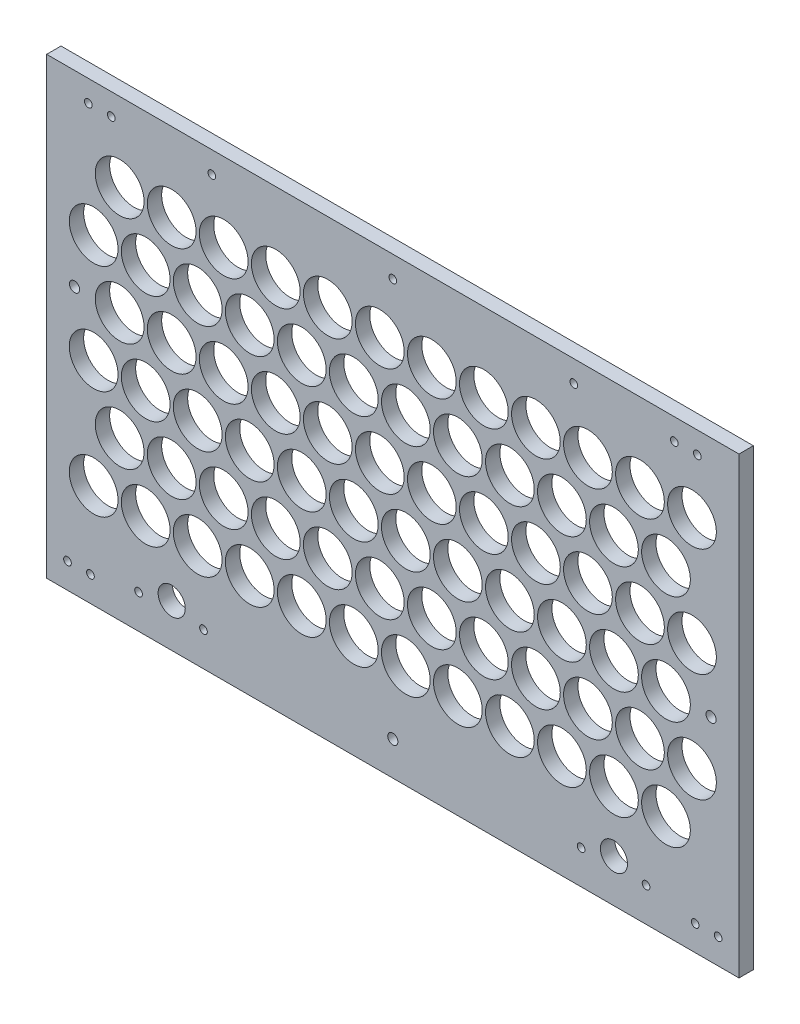
SolidWorks part; units mm, degrees
material "ABS"
ref_plane "X-Y Datum" through (0, 0, 0) normal (0, 0, 1) x (1, 0, 0)
ref_plane "X-Z Datum" through (0, 0, 0) normal (0, 1, 0) x (1, 0, 0)
ref_plane "Y-Z Datum" through (0, 0, 0) normal (1, 0, 0) x (0, 0, -1)
sketch "Sketch1" plane through (0, 0, 0) normal (0, 0, 1) x (1, 0, 0)
  line L1 (-143.025, 70.775) -> (143.025, 70.775)
  line L2 (-143.025, 70.775) -> (-143.025, -70.775)
  line L3 (-143.025, -70.775) -> (143.025, -70.775)
  line L4 (143.025, 70.775) -> (143.025, -70.775)
  line L5 (-143.025, 70.775) -> (143.025, -70.775) construction
  line L6 (-143.025, -70.775) -> (143.025, 70.775) construction
  line L13 (-153.025, -105.775) -> (153.025, -105.775)
  line L14 (-153.025, 91.65) -> (153.025, 91.65)
  line L15 (-153.025, 91.65) -> (-153.025, -105.775)
  line L16 (153.025, 91.65) -> (153.025, -105.775)
  line L17 (153.025, 70.775) -> (153.025, -70.775) construction
  line L18 (-143.025, 91.65) -> (143.025, 91.65) construction
  line L19 (-143.025, -105.775) -> (143.025, -105.775) construction
  line L20 (-153.025, 70.775) -> (-153.025, -70.775) construction
  line L21 (-132.25, -60) -> (-109.25, -60) construction
  circle A0 centre (-132.25, -60) radius 10.775
  circle A1 centre (-109.25, -60) radius 10.775 construction
  circle A2 centre (-120.75, -36) radius 10.775
  point P0 (0, 0)
  point P16 (-120.75, -60)
  dimension "D1" = 21.55
  dimension "D2" = 23
  dimension "D3" = 24
  dimension "D5" = 141.55
  dimension "D6" = 286.05
  dimension "D7" = 35
  dimension "D8" = 20.875
  dimension "D9" = 10
  dimension "D10" = 10
extrude "Boss-Extrude1" add sketch "Sketch1" along normal blind 6.35 contours A0 L3 L4 L1 L2 A2 | A2 | A0 | A0 L2 L3 | L1 L4 L3 L2 region at (2.4105, 0.9241, 0) region at (-140.6182, -68.3682, 0) region at (-132.25, -60, 0) region at (-149.383, -7.0625, 0) region at (-120.75, -36, 0)
sketch "Sketch3" plane through (0, 0, 6.35) normal (0, 0, 1) x (1, 0, 0)
  line L4 (143.025, 70.775) -> (-143.025, 70.775)
  line L5 (143.025, -70.775) -> (143.025, 70.775)
  line L6 (-143.025, -70.775) -> (143.025, -70.775)
  line L7 (-143.025, 70.775) -> (-143.025, -70.775)
  line L8 (143.025, 70.775) -> (-143.025, 70.775)
  line L9 (143.025, -70.775) -> (143.025, 70.775)
  line L10 (-143.025, -70.775) -> (143.025, -70.775)
  line L11 (-143.025, 70.775) -> (-143.025, -70.775)
  circle A1 centre (-120.75, -36) radius 10.775
  circle A2 centre (-120.75, -36) radius 10.775
  circle A3 centre (-132.25, -60) radius 10.775
  circle A4 centre (-132.25, -60) radius 10.775
  dimension "D1" = 0
  dimension "D2" = 0
  dimension "D3" = 0
extrude "Cut-Extrude1" cut sketch "Sketch3" against normal through all contours A4 region at (-132.25, -60, 6.35)
sketch "Sketch4" plane through (0, 0, 6.35) normal (0, 0, 1) x (1, 0, 0)
  line L4 (143.025, 70.775) -> (-143.025, 70.775)
  line L5 (143.025, -70.775) -> (143.025, 70.775)
  line L6 (-143.025, -70.775) -> (143.025, -70.775)
  line L7 (-143.025, 70.775) -> (-143.025, -70.775)
  line L8 (143.025, 70.775) -> (-143.025, 70.775)
  line L9 (143.025, -70.775) -> (143.025, 70.775)
  line L10 (-143.025, -70.775) -> (143.025, -70.775)
  line L11 (-143.025, 70.775) -> (-143.025, -70.775)
  circle A1 centre (-120.75, -36) radius 10.775
  circle A2 centre (-120.75, -36) radius 10.775
  circle A3 centre (-132.25, -60) radius 10.775
  circle A4 centre (-132.25, -60) radius 10.775
  dimension "D1" = 0
  dimension "D2" = 0
  dimension "D3" = 0
extrude "Cut-Extrude2" cut sketch "Sketch4" against normal through all contours A2 region at (-120.75, -36, 6.35)
pattern_linear "LPattern1" count 12 spacing 23 along (1, 0, 0) of "Cut-Extrude1", "Cut-Extrude2"
pattern_linear "LPattern2" count 3 spacing 48 along (0, 1, 0) of "LPattern1"
sketch "Sketch5" plane through (0, 0, 0) normal (0, 0, -1) x (-1, 0, 0)
sketch "Sketch13" plane through (0, 91.65, 0) normal (0, 1, 0) x (1, 0, 0)
  line L4 (153.025, 0) -> (-153.025, 0)
  line L5 (-153.025, 0) -> (-153.025, -6.35)
  line L6 (-153.025, -6.35) -> (153.025, -6.35)
  line L7 (153.025, -6.35) -> (153.025, 0)
  line L8 (153.025, 0) -> (-153.025, 0)
  line L9 (-153.025, 0) -> (-153.025, -6.35)
  line L10 (-153.025, -6.35) -> (153.025, -6.35)
  line L11 (153.025, -6.35) -> (153.025, 0)
  dimension "D1" = 0
extrude "Boss-Extrude2" add sketch "Sketch13" along normal blind 3.175
sketch "Sketch14" plane through (0, 0, 0) normal (0, 0, -1) x (-1, 0, 0)
  circle A0 centre (-97.75, -86.775) radius 6
extrude "Cut-Extrude3" cut sketch "Sketch14" against normal through all
mirror "Mirror1" about plane through (0, 0, 0) normal (1, 0, 0) of "Cut-Extrude3"
sketch "Sketch15" plane through (0, 0, 0) normal (0, 0, -1) x (-1, 0, 0)
  point P0 (-111.94, -90.775)
  point P1 (-83.25, -90.775)
  point P3 (83.712, -90.775)
  point P7 (134.61, 85.3)
  point P9 (124.45, 85.3)
  point P11 (80, 85.3)
  point P13 (0, 85.3)
  point P15 (-80, 85.3)
  point P17 (-124.45, 85.3)
  point P19 (-134.61, 85.3)
  point P25 (143.8175, -94.6)
  point P27 (133.6575, -94.6)
  point P29 (-133.6575, -94.6)
  point P31 (-143.8175, -94.6)
  point P41 (112.402, -90.775)
hole_wizard "M3 Clearance Hole1" positions "Sketch15" profile "Sketch16" hole size "M3" standard "ANSI Metric" end condition through all
sketch "Sketch16" plane through (111.94, -90.775, 0) normal (1, 0, 0) x (0, 1, 0)
  line L0 (0, 0) -> (0, 6.35)
  line L1 (0, 6.35) -> (1.7, 6.35)
  line L2 (1.7, 6.35) -> (1.7, 0)
  line L5 (1.7, 0) -> (0, 0)
  line L11 (0, -6.35) -> (0, 107.95) construction
  dimension "Thru Hole Dia." = 3.4
  dimension "Thru Hole Depth" = 6.35
sketch "Sketch17" plane through (0, 0, 0) normal (0, 0, -1) x (-1, 0, 0)
  line L0 (0, -105.775) -> (0, -77.9164) construction
  line L1 (153.025, -105.775) -> (-153.025, -105.775) construction
  circle A0 centre (0, -90.775) radius 2.25
  circle A1 centre (140.6875, 12) radius 2.25
  circle A2 centre (-140.6875, -12) radius 2.25
  point P0 (-140.6875, -12)
  point P1 (140.6875, 12)
  point P9 (0, -90.775)
  point P11 (83.712, -90.775)
  dimension "D1" = 4.5
extrude "Cut-Extrude4" cut sketch "Sketch17" against normal through all
